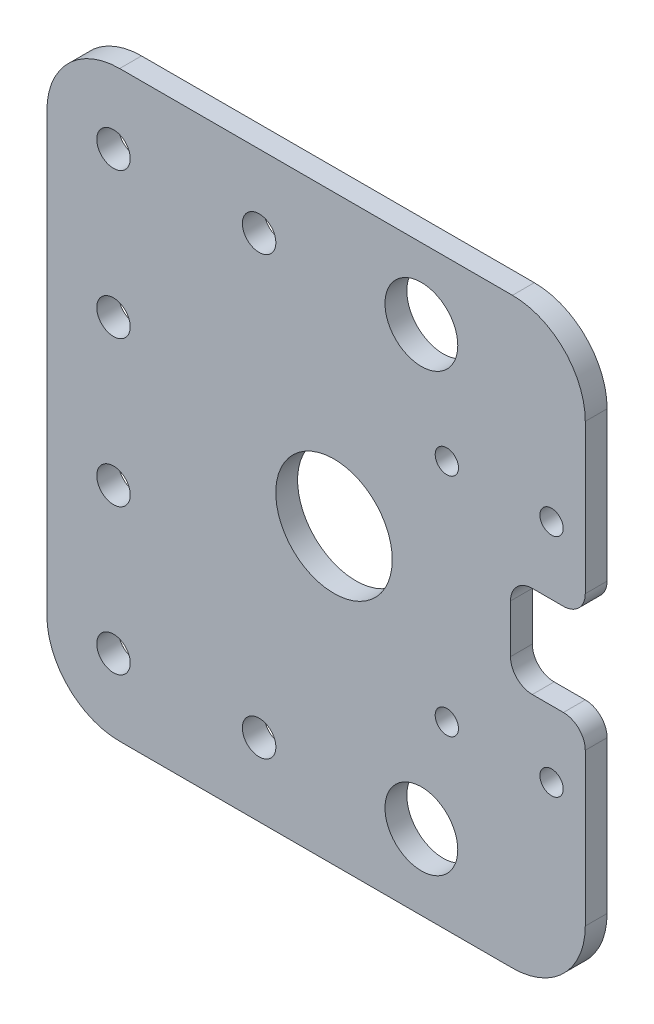
SolidWorks part; units mm, degrees
ref_plane "Front Plane" through (0, 0, 0) normal (0, 0, 1) x (1, 0, 0)
ref_plane "Top Plane" through (0, 0, 0) normal (0, 1, 0) x (1, 0, 0)
ref_plane "Right Plane" through (0, 0, 0) normal (1, 0, 0) x (0, 0, -1)
sketch "Sketch1" plane through (0, 0, 0) normal (0, 0, 1) x (1, 0, 0)
  line L0 (157.9607, -71.8662) -> (170.4739, -71.8662)
  line L1 (116.5258, -71.8662) -> (157.9607, -71.8662)
  line L2 (106.5258, -81.8662) -> (106.5258, -141.8968)
  line L3 (116.5258, -151.8968) -> (157.9607, -151.8968)
  line L4 (180.4739, -81.8662) -> (180.4739, -102.3655)
  line L5 (145.9607, -111.5917) -> (157.9607, -111.5917) construction
  line L6 (157.9607, -111.5917) -> (157.9607, -81.5917) construction
  line L7 (157.9607, -111.5917) -> (157.9607, -141.5917) construction
  line L8 (170.4739, -151.8968) -> (157.9607, -151.8968)
  line L9 (180.4739, -120.9895) -> (180.4739, -141.8968)
  line L10 (180.4739, -102.3655) -> (180.4739, -105.3655)
  line L11 (180.4739, -105.3655) -> (170.1989, -105.3655)
  line L12 (170.1989, -133.8871) -> (170.1989, -89.8565) construction
  line L13 (180.4739, -120.9895) -> (180.4739, -117.9895)
  line L14 (180.4739, -117.9895) -> (170.1989, -117.9895)
  line L15 (170.1989, -105.3655) -> (170.1989, -117.9895)
  circle A0 centre (115.6746, -101.8662) radius 2.3
  circle A1 centre (115.6746, -121.8662) radius 2.3
  circle A2 centre (135.6746, -141.8662) radius 2.3
  circle A3 centre (135.6746, -81.8662) radius 2.3
  circle A4 centre (115.6746, -81.8662) radius 2.3
  circle A5 centre (115.6746, -141.8662) radius 2.3
  circle A6 centre (161.4607, -96.1142) radius 1.6
  circle A7 centre (161.4607, -127.1142) radius 1.6
  arc A9 (180.4739, -141.8968) -> (170.4739, -151.8968) centre (170.4739, -141.8968) cw
  circle A10 centre (145.9607, -111.5917) radius 8
  arc A11 (180.4739, -81.8662) -> (170.4739, -71.8662) centre (170.4739, -81.8662) ccw
  circle A12 centre (175.8433, -96.1142) radius 1.6
  arc A13 (106.5258, -141.8968) -> (116.5258, -151.8968) centre (116.5258, -141.8968) ccw
  arc A14 (116.5258, -71.8662) -> (106.5258, -81.8662) centre (116.5258, -81.8662) ccw
  circle A15 centre (157.9607, -81.5917) radius 5
  circle A16 centre (157.9607, -141.5917) radius 5
  circle A17 centre (175.8433, -127.1142) radius 1.6
  point P47 (106.5258, -71.8662)
  dimension "D1" = 10
  dimension "D4" = 12
  dimension "D5" = 3
  dimension "D2" = 30
  dimension "D3" = 30
  dimension "D6" = 3
extrude "Boss-Extrude1" add sketch "Sketch1" along normal blind 3
fillet "Fillet1" radius 3 4 edges at (170.1989, -117.9895, 1.5) (180.4739, -117.9895, 1.5) (170.1989, -105.3655, 1.5) (180.4739, -105.3655, 1.5)
